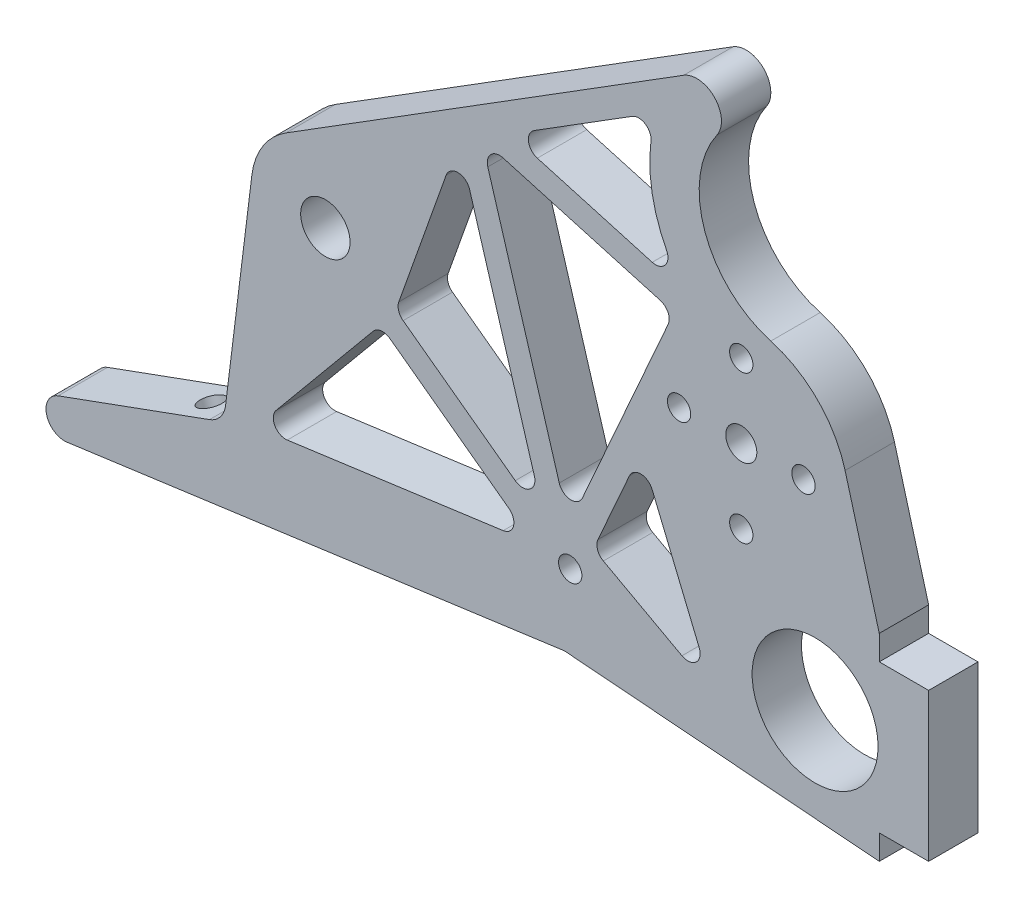
SolidWorks part; units mm, degrees
ref_plane "Front Plane" through (0, 0, 0) normal (0, 0, 1) x (1, 0, 0)
ref_plane "Top Plane" through (0, 0, 0) normal (0, 1, 0) x (1, 0, 0)
ref_plane "Right Plane" through (0, 0, 0) normal (1, 0, 0) x (0, 0, -1)
sketch "Sketch1" plane through (0, 0, 0) normal (0, 0, 1) x (1, 0, 0)
  line L0 (14.5951, 62.2929) -> (-36.5475, 30.3002)
  line L1 (0, -55) -> (0, 55) construction
  line L2 (39.751, 9.525) -> (46.101, 9.525)
  line L3 (39.751, 9.525) -> (39.751, -9.525) construction
  line L4 (39.751, -9.525) -> (46.101, -9.525)
  line L5 (46.101, 9.525) -> (46.101, -9.525)
  line L6 (14.0023, 24.9685) -> (30.0023, 24.9685) construction
  line L7 (22.0023, 34.4685) -> (22.0023, 15.4685) construction
  line L8 (39.751, 9.525) -> (39.751, 12.7)
  line L9 (39.751, -9.525) -> (39.751, -12.7)
  line L10 (-36.9877, 14.4425) -> (-5.4917, -7.7825)
  line L11 (39.751, -12.7) -> (-0.7513, -9.4953)
  line L12 (-11.2218, 115.1427) -> (23226.9166, -41331.4577) construction
  line L14 (22.0023, 24.9685) -> (35.1908, 32.363) construction
  line L15 (39.751, 12.7) -> (35.3543, 28.6493)
  line L16 (22.0023, 24.9685) -> (24.7256, 17.8063)
  line L17 (24.7256, 17.8063) -> (26.9246, 12.0227) construction
  line L18 (26.9246, 12.0227) -> (28.6172, 7.5712)
  line L19 (28.6172, 7.5712) -> (31.496, 0) construction
  circle A2 centre (31.496, 0) radius 19.05 construction
  circle A3 centre (-31.496, 0) radius 19.05 construction
  circle A4 centre (-31.496, 22.225) radius 38.1 construction
  circle A5 centre (0, 0) radius 1.5
  circle A6 centre (22.0023, 34.4685) radius 1.5
  circle A7 centre (30.0023, 24.9685) radius 1.5
  circle A8 centre (22.0023, 15.4685) radius 1.5
  circle A9 centre (14.0023, 24.9685) radius 1.5
  circle A11 centre (-31.496, 22.225) radius 3.175
  arc A12 (-36.5475, 30.3002) -> (-36.9877, 14.4425) centre (-31.496, 22.225) ccw
  arc A19 (35.3543, 28.6493) -> (25.8019, 38.2871) centre (22.0023, 24.9685) ccw
  arc A20 (18.8804, 57.7809) -> (14.5951, 62.2929) centre (16.279, 59.6012) ccw
  arc A21 (-5.4917, -7.7825) -> (-0.7513, -9.4953) centre (0, 0) ccw
  arc A22 (18.8804, 57.7809) -> (25.8019, 38.2871) centre (29.286, 50.4999) ccw
  arc A23 (-36.9877, 14.4425) -> (-36.5475, 30.3002) centre (-31.496, 22.225) ccw construction
  circle A31 centre (22.0023, 24.9685) radius 2
  arc A33 (4.086, 8.6041) -> (-5.4917, -7.7825) centre (0, 0) ccw construction
  arc A34 (-0.7513, -9.4953) -> (4.086, 8.6041) centre (0, 0) ccw construction
  arc A35 (25.8019, 38.2871) -> (16.8069, 12.1299) centre (22.0023, 24.9685) ccw construction
  arc A36 (16.8069, 12.1299) -> (35.3543, 28.6493) centre (22.0023, 24.9685) ccw construction
  circle A37 centre (31.496, 0) radius 8.1
  point P2 (34.083, 31.7419)
  point P10 (46.101, 0)
  point P13 (-31.496, -19.05)
  point P24 (-31.496, -15.875)
  point P26 (22.0023, 24.9685)
  point P29 (22.0023, 24.9685)
  point P37 (42.926, -9.525)
  point P53 (22.0686, 21.567)
  point P54 (22.0686, 21.567)
  point P55 (27.371, 8.6041)
  point P57 (22.0707, 21.7757)
  point P58 (22.7178, 22.0445)
  point P59 (22.0621, 23.2866)
  point P60 (0, 0)
  dimension "D7" = 38.1
  dimension "D8" = 76.2
  dimension "D11" = 3
  dimension "D13" = 3
  dimension "D14" = 27.7
  dimension "D16" = 6.35
  dimension "D17" = 19.05
  dimension "D21" = 6.35
  dimension "D22" = 1.27
  dimension "D23" = 16.2
  dimension "D25" = 12.7
  dimension "D26" = 4
  dimension "D19" = 19.05
  dimension "D24" = 60.325
  dimension "D3" = 19.05
  dimension "D4" = 6.35
  dimension "D5" = 11.43
  dimension "D6" = 62.992
  dimension "D9" = 3.175
  dimension "D10" = 19
  dimension "D12" = 16
  dimension "D15" = 4.7625
  dimension "D18" = 53.5686
  dimension "D20" = 3.175
extrude "Boss-Extrude1" add sketch "Sketch1" along normal mid plane 6.35 contours L10 L11 L9 L4 L5 L2 L8 A12 A20 A6 A7 A8 A9 A11 region at (4.0632, 20.2142, 0)
sketch "Sketch2" plane through (0, 0, 3.175) normal (0, 0, 1) x (1, 0, 0)
  line L0 (-46.398, -6.562) -> (-65.8615, -13.6461) construction
  line L1 (-46.398, -6.562) -> (-65.8615, -13.6461)
  line L2 (-44.3329, -3.9682) -> (-40.949, 23.3941)
  line L3 (-64.7244, -18.2431) -> (-0.7513, -9.4953)
  line L4 (-36.9877, 14.4425) -> (-5.4917, -7.7825) construction
  line L5 (-36.9877, 14.4425) -> (-5.4917, -7.7825)
  arc A0 (-65.8615, -13.6461) -> (-64.8428, -18.2563) centre (-65.0471, -15.8838) ccw construction
  arc A1 (-65.8615, -13.6461) -> (-64.7244, -18.2431) centre (-65.0471, -15.8838) ccw
  arc A2 (-5.4917, -7.7825) -> (-0.7513, -9.4953) centre (0, 0) ccw construction
  arc A3 (-46.398, -6.562) -> (-44.3329, -3.9682) centre (-47.4839, -3.5785) ccw
  arc A4 (-36.5475, 30.3002) -> (-36.9877, 14.4425) centre (-31.496, 22.225) ccw construction
  arc A5 (-5.4917, -7.7825) -> (-0.7513, -9.4953) centre (0, 0) ccw
  arc A6 (-40.949, 23.3941) -> (-36.9877, 14.4425) centre (-31.496, 22.225) ccw
  dimension "D1" = 3.175
extrude "Boss-Extrude2" add sketch "Sketch2" against normal up to surface (6.35 mm away) up to face at (39.596, 0, -3.175)
sketch "Sketch3" plane through (-3.3185, 9.1176, 0) normal (-0.342, 0.9397, 0) x (0.9397, 0.342, 0)
  line L0 (-45.8442, 3.175) -> (-45.8442, -3.175) construction
  line L1 (-49.0192, 0) -> (-45.8442, 0) construction
  circle A0 centre (-49.0192, 0) radius 1.5
  dimension "D1" = 3
  dimension "D2" = 3.175
extrude "Cut-Extrude1" cut sketch "Sketch3" against normal blind 6
sketch "Sketch4" plane through (0, 0, -3.175) normal (0, 0, -1) x (-1, 0, 0)
  line L0 (-11.1755, 56.4087) -> (7.6665, 44.6219)
  line L1 (11.4374, 42.263) -> (0.1766, 4.7592)
  line L2 (3.2419, 3.4888) -> (14.3391, 40.4478)
  line L4 (-13.3374, 35.2112) -> (0.1766, 4.7592)
  line L8 (-31.496, 0) -> (-18.317, -4.6342) construction
  line L9 (-14.5951, 62.2929) -> (36.5475, 30.3002) construction
  line L10 (-14.5951, 62.2929) -> (36.5475, 30.3002)
  line L11 (-11.1755, 56.4087) -> (-9.4917, 59.1004) construction
  line L12 (-9.113, 17.554) -> (-18.317, -4.6342)
  line L13 (14.3391, 40.4478) -> (22.4426, 17.6139)
  line L14 (3.2419, 3.4888) -> (22.4426, 17.6139)
  line L15 (24.3988, 14.9548) -> (4.7372, 0.4906)
  line L16 (4.2381, 2.1726) -> (31.496, 22.225) construction
  line L17 (14.8849, 7.9559) -> (12.9287, 10.615) construction
  line L18 (4.7372, 0.4906) -> (40.4309, -4.3902)
  line L19 (0.7513, -9.4953) -> (64.7244, -18.2431) construction
  line L20 (11.4374, 42.263) -> (-13.3374, 35.2112)
  line L21 (-14.6897, 38.2585) -> (7.6665, 44.6219)
  line L22 (-3.5116, 41.4402) -> (-2.6079, 38.2652) construction
  line L23 (7.6665, 44.6219) -> (11.4374, 42.263) construction
  line L25 (8.9687, 22.5618) -> (5.807, 23.5111) construction
  line L26 (-14.6897, 38.2585) -> (-13.3374, 35.2112) construction
  line L28 (24.3988, 14.9548) -> (40.4309, -4.3902)
  line L29 (-10.5833, 46.8787) -> (-16.8175, 48.0858) construction
  line L31 (46.398, -6.562) -> (40.4309, -4.3902) construction
  line L32 (65.8615, -13.6461) -> (46.398, -6.562) construction
  line L33 (-18.317, -4.6342) -> (-2.9737, 3.72)
  line L34 (-2.9737, 3.72) -> (-9.113, 17.554)
  line L35 (-2.8398, 11.5564) -> (-5.8572, 10.2174) construction
  line L36 (-39.751, -12.7) -> (0.7513, -9.4953) construction
  arc A1 (-14.6897, 38.2585) -> (-11.1755, 56.4087) centre (-29.286, 50.4999) ccw
  arc A2 (-25.8019, 38.2871) -> (-18.8804, 57.7809) centre (-29.286, 50.4999) ccw construction
  circle A3 centre (-31.496, 0) radius 8.1 construction
  circle A4 centre (-31.496, 0) radius 8.1
  circle A5 centre (0, 0) radius 4.7625 construction
  arc A6 (23.312, 16.2044) -> (24.3988, 14.9548) centre (31.496, 22.225) ccw construction
  arc A7 (22.4426, 17.6139) -> (23.312, 16.2044) centre (31.496, 22.225) ccw construction
  circle A8 centre (-14.0023, 24.9685) radius 1.5 construction
  point P34 (13.9068, 9.2854)
  point P48 (-11.2949, 56.4087)
  point P49 (8.0202, 45.2071)
  point P50 (-16.2229, 36.6342)
  point P53 (11.7628, 43.0154)
  point P54 (-14.5951, 33.5053)
  dimension "D5" = 9.525
  dimension "D11" = 8.8815
  dimension "D1" = 6.35
  dimension "D2" = 3.175
  dimension "D3" = 10.16
  dimension "D4" = 4.7625
  dimension "D6" = 3.175
  dimension "D7" = 6.35
  dimension "D8" = 22.225
  dimension "D9" = 13.97
  dimension "D10" = 6.35
extrude "Cut-Extrude2" cut sketch "Sketch4" against normal through all and the other way through all contours A1 L21 L0 | L1 L20 L4 | L2 L14 | L15 | L33 L34 L12 region at (4.9727, 46.2965, -3.175) region at (0.5745, 27.4111, -3.175) region at (-13.3412, 20.5168, -3.175) region at (10.1346, 5.5466, -3.175) region at (-23.189, 3.6851, -3.175)
fillet "Fillet1" radius 1.5875 15 edges at (-7.6665, 44.6219, 0) (11.1755, 56.4087, 0) (13.3374, 35.2112, 0) (-11.4374, 42.263, 0) (-22.4426, 17.6139, 0) (-14.3391, 40.4478, 0) (-24.3988, 14.9548, 0) (-3.2419, 3.4888, 0) (-0.1766, 4.7592, 0) (14.6897, 38.2585, 0) (2.9737, 3.72, 0) (9.113, 17.554, 0) (18.317, -4.6342, 0) (-40.4309, -4.3902, 0) (-4.7372, 0.4906, 0)
